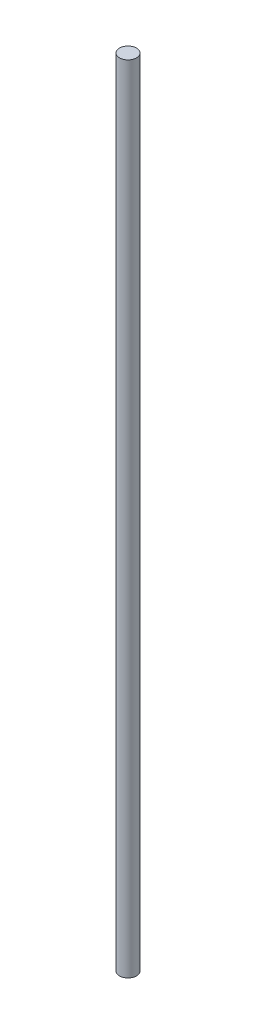
SolidWorks part; units mm, degrees
ref_plane "前视基准面" through (0, 0, 0) normal (0, 0, 1) x (1, 0, 0)
ref_plane "上视基准面" through (0, 0, 0) normal (0, 1, 0) x (1, 0, 0)
ref_plane "右视基准面" through (0, 0, 0) normal (1, 0, 0) x (0, 0, -1)
sketch "草图1" plane through (0, 0, 0) normal (0, 1, 0) x (1, 0, 0)
  circle A0 centre (0, 0) radius 1.5
  dimension "D1" = 3
extrude "凸台-拉伸1" add sketch "草图1" along normal blind 140
